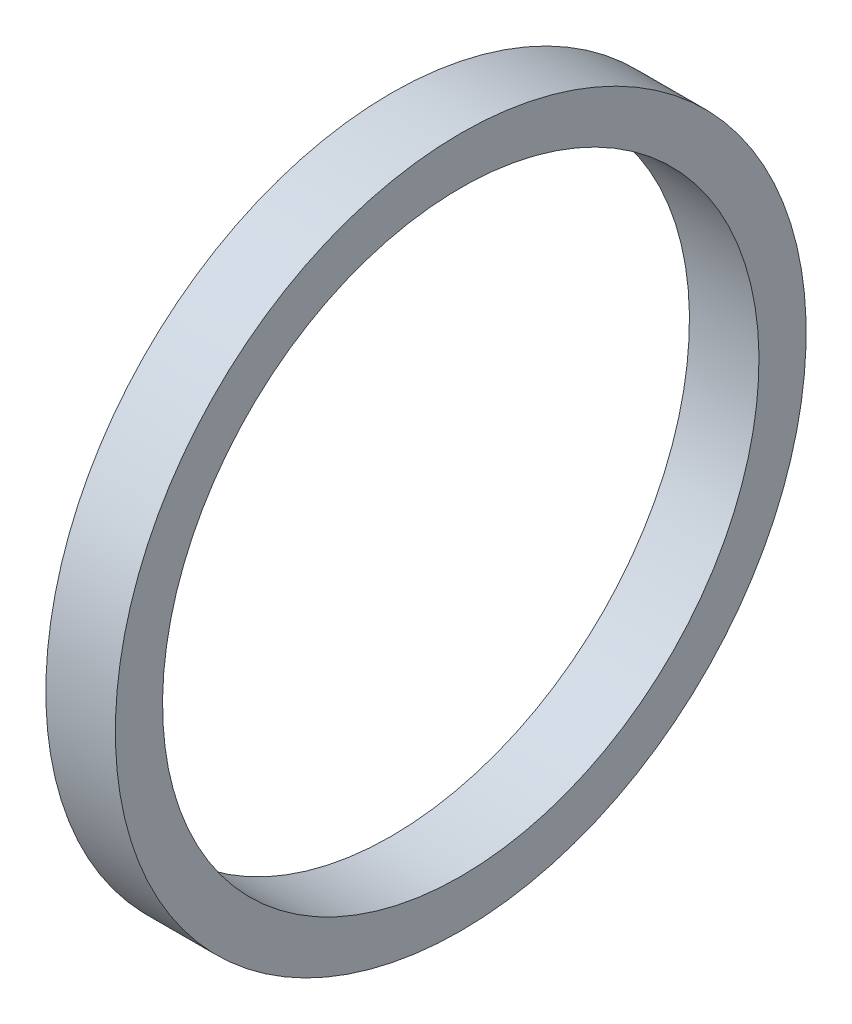
SolidWorks part; units mm, degrees
material "6061-T6 (SS)"
ref_plane "Front Plane" through (0, 0, 0) normal (0, 0, 1) x (1, 0, 0)
ref_plane "Top Plane" through (0, 0, 0) normal (0, 1, 0) x (1, 0, 0)
ref_plane "Right Plane" through (0, 0, 0) normal (1, 0, 0) x (0, 0, -1)
sketch "Sketch1" plane through (-24.6156, 0, 0) normal (-1, 0, 0) x (0, 0, 1)
  circle A0 centre (0, 0) radius 13.9746 construction
  circle A1 centre (0, 0) radius 13.9746
  circle A2 centre (0, 0) radius 12.065
  dimension "D1" = 24.13
extrude "Boss-Extrude1" add sketch "Sketch1" along normal up to surface (2.8125 mm away)
